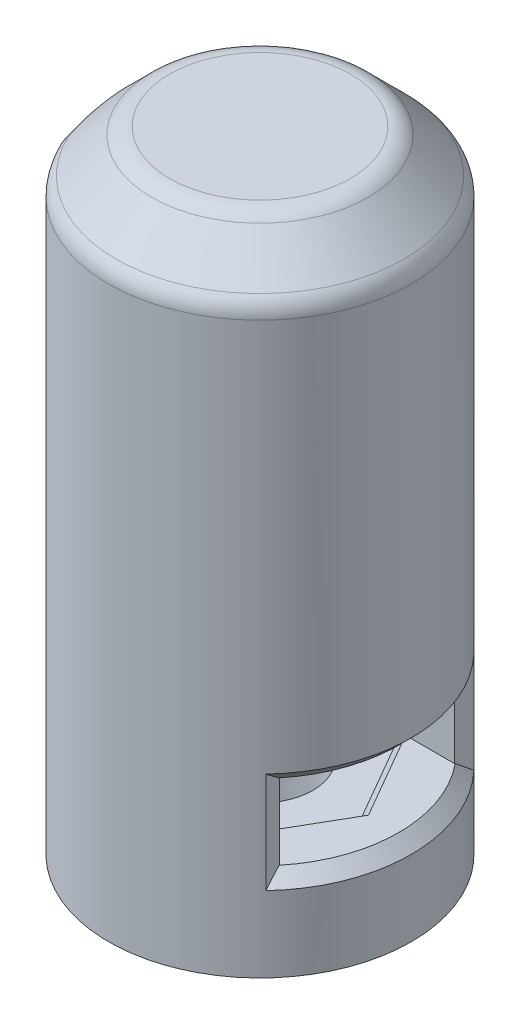
SolidWorks part; units mm, degrees
material "ABS"
ref_plane "Front Plane" through (0, 0, 0) normal (0, 0, 1) x (1, 0, 0)
ref_plane "Top Plane" through (0, 0, 0) normal (0, 1, 0) x (1, 0, 0)
ref_plane "Right Plane" through (0, 0, 0) normal (1, 0, 0) x (0, 0, -1)
sketch "Sketch1" plane through (0, 0, 0) normal (0, 1, 0) x (1, 0, 0)
  circle A0 centre (0, 0) radius 6
  dimension "D1" = 12
extrude "Base Extrude" add sketch "Sketch1" along normal mid plane 25
chamfer "Top Chemfer" distance 2 angle 45 1 edges at (0, 12.5, 6)
sketch "Sketch2" plane through (0, 0, 0) normal (1, 0, 0) x (0, 0, -1)
  line L0 (6, -12.5) -> (6, 10.5) construction
  line L1 (-6, -12.5) -> (6, -12.5)
  line L2 (-6, -12.5) -> (-6, 12.5)
  line L3 (-6, 12.5) -> (6, 12.5)
  line L4 (6, -12.5) -> (6, 12.5)
  line L5 (4, 12.5) -> (-4, 12.5) construction
extrude "Side Flatten Cut" cut sketch "Sketch2" against normal blind 25 from offset 5.5 offset against normal yes
fillet "Edges Fillet" radius 1 5 edges at (0, 12.5, 4) (6, 10.5, 0) (-5.5, -1, 2.3979) (-5.5, 10.9993, 0.0859) (-5.5, -1, -2.3979)
sketch "Sketch3" plane through (0, 0, 0) normal (0, 1, 0) x (1, 0, 0)
  line L1 (2.0063, -3.475) -> (4.0126, 0)
  line L2 (4.0126, 0) -> (2.0063, 3.475)
  line L3 (2.0063, 3.475) -> (-2.0063, 3.475)
  line L4 (-2.0063, 3.475) -> (-4.0126, 0)
  line L5 (-4.0126, 0) -> (-2.0063, -3.475)
  line L6 (-2.0063, -3.475) -> (2.0063, -3.475)
  circle A0 centre (0, 0) radius 3.475 construction
  dimension "D1" = 6.95
extrude "Nut Cut" cut sketch "Sketch3" against normal blind 3.25 from offset 6 offset against normal yes
sketch "Sketch5" plane through (0, 0, 0) normal (1, 0, 0) x (0, 0, -1)
  line L0 (0, -6) -> (-3.475, -6) construction
  line L1 (-3.475, -6) -> (3.475, -6)
  line L2 (-3.475, -6) -> (-3.475, -9)
  line L3 (-3.475, -9) -> (3.475, -9)
  line L4 (3.475, -6) -> (3.475, -9)
  point P6 (0, -6)
  point P7 (0, 0)
  dimension "D1" = 3
  dimension "D2" = 6.95
extrude "Nut Insert Cut" cut sketch "Sketch5" along normal through all
chamfer "Nut Insert Chamfer 1" distance 0.25 angle 45 2 edges at (3.0094, -9, 1.7375) (3.0094, -9, -1.7375)
chamfer "Nut Insert Chamfer 2" distance 0.5 angle 45 2 edges at (6, -9, 0) (6, -6, 0)
chamfer "Nut Insert Chamfer 3" distance 0.9 angle 45 2 edges at (4.8913, -7.5, -3.475) (4.8913, -7.5, 3.475) first distance on face at (0.3, -1.2071, 0)
sketch "Sketch6" plane through (0, -12.5, 0) normal (0, -1, 0) x (1, 0, 0)
  circle A0 centre (0, 0) radius 2.1
  dimension "D1" = 4.2
extrude "Bolt Cut" cut sketch "Sketch6" against normal blind 20
